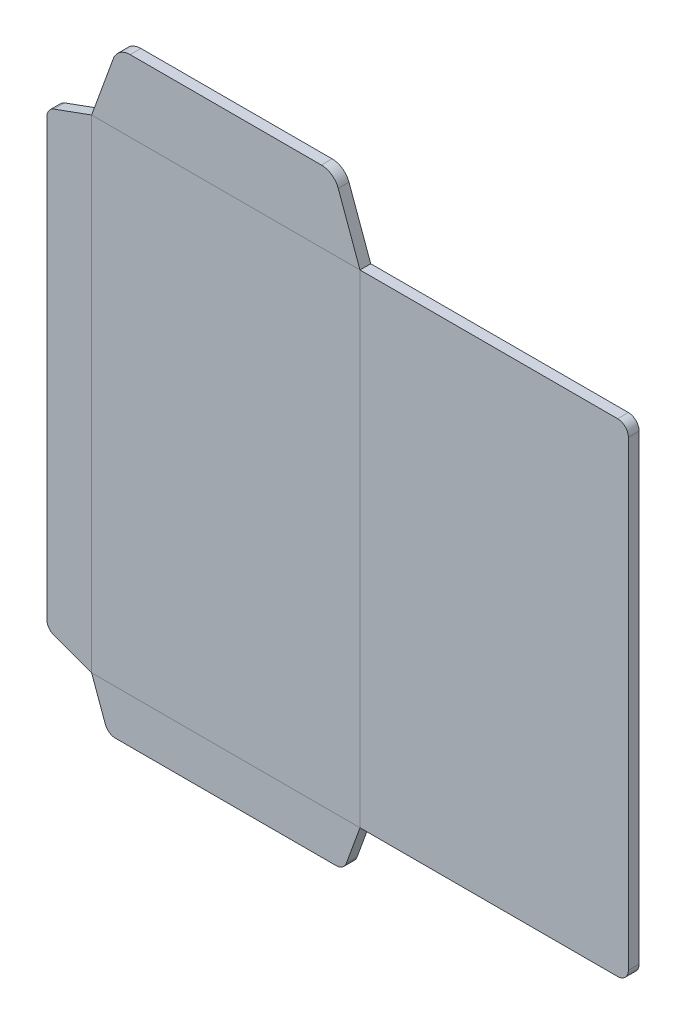
SolidWorks part; units mm, degrees
ref_plane "Front" through (0, 0, 0) normal (0, 0, 1) x (1, 0, 0)
ref_plane "Top" through (0, 0, 0) normal (0, 1, 0) x (1, 0, 0)
ref_plane "Right" through (0, 0, 0) normal (1, 0, 0) x (0, 0, -1)
sketch "Esquisse1" plane through (0, 0, 0) normal (0, 0, 1) x (1, 0, 0)
  line L1 (0, 0) -> (75, 0)
  line L2 (0, 0) -> (0, 135)
  line L3 (0, 135) -> (75, 135)
  line L4 (75, 0) -> (75, 135)
  dimension "D1" = 75
  dimension "D2" = 135
extrude "Boss.-Extru.1" add sketch "Esquisse1" along normal blind 3
sketch "Esquisse2" plane through (0, 0, 3) normal (0, 0, 1) x (1, 0, 0)
  line L0 (0, 0) -> (-12.5, 4.5496)
  line L1 (-12.5, 4.5496) -> (-12.5, 130.4504)
  line L2 (-12.5, 67.5) -> (0, 67.5) construction
  line L3 (0, 135) -> (0, 0) construction
  line L4 (0, 135) -> (-12.5, 130.4504)
  line L5 (37.5, 0) -> (37.5, -12.5) construction
  line L6 (0, 0) -> (75, 0) construction
  line L7 (70.4504, -12.5) -> (4.5496, -12.5)
  line L8 (4.5496, -12.5) -> (0, 0)
  line L9 (70.4504, -12.5) -> (75, 0)
  line L10 (75, 0) -> (0, 0)
  line L11 (0, 0) -> (0, 135)
  line L12 (75, 135) -> (67.7206, 155)
  line L13 (75, 135) -> (0, 135) construction
  line L14 (75, 0) -> (75, 135) construction
  line L15 (67.7206, 155) -> (7.2794, 155)
  line L16 (37.5, 155) -> (37.5, 135) construction
  line L17 (0, 135) -> (7.2794, 155)
  line L18 (0, 135) -> (75, 135)
  line M10 (0, 135) -> (0, 0)
  line M11 (0, 0) -> (75, 0)
  line M13 (75, 135) -> (0, 135)
  dimension "D1" = 12.5
  dimension "D2" = 70
  dimension "D3" = 70
  dimension "D4" = 20
  dimension "D5" = 70
extrude "Boss.-Extru.2" add sketch "Esquisse2" against normal up to vertex (3 mm away) separate body contours L17 L12 L15 M13 | L4 L1 L0 M10 | L7 L9 L8 M11 region at (37.5, 144.6417, 3) region at (37.5, -6.1155, 3) region at (-6.1773, 67.5, 3) up to point (75, 135, 0)
fillet "Congé1" radius 3 2 edges at (-12.5, 4.5496, 1.5) (-12.5, 130.4504, 1.5)
fillet "Congé2" radius 3 2 edges at (70.4504, -12.5, 1.5) (4.5496, -12.5, 1.5)
fillet "Congé3" radius 5 2 edges at (7.2794, 155, 1.5) (67.7206, 155, 1.5)
sketch "Esquisse3" plane through (0, 0, 3) normal (0, 0, 1) x (1, 0, 0)
  line L0 (75, 135) -> (0, 135) construction
  line L1 (75, 0) -> (150, 0)
  line L2 (75, 0) -> (75, 135)
  line L3 (75, 135) -> (150, 135)
  line L4 (150, 0) -> (150, 135)
extrude "Boss.-Extru.3" add sketch "Esquisse3" against normal up to vertex (3 mm away) separate body up to point (75, 0, 0)
fillet "Congé4" radius 3 2 edges at (150, 0, 1.5) (150, 135, 1.5)
